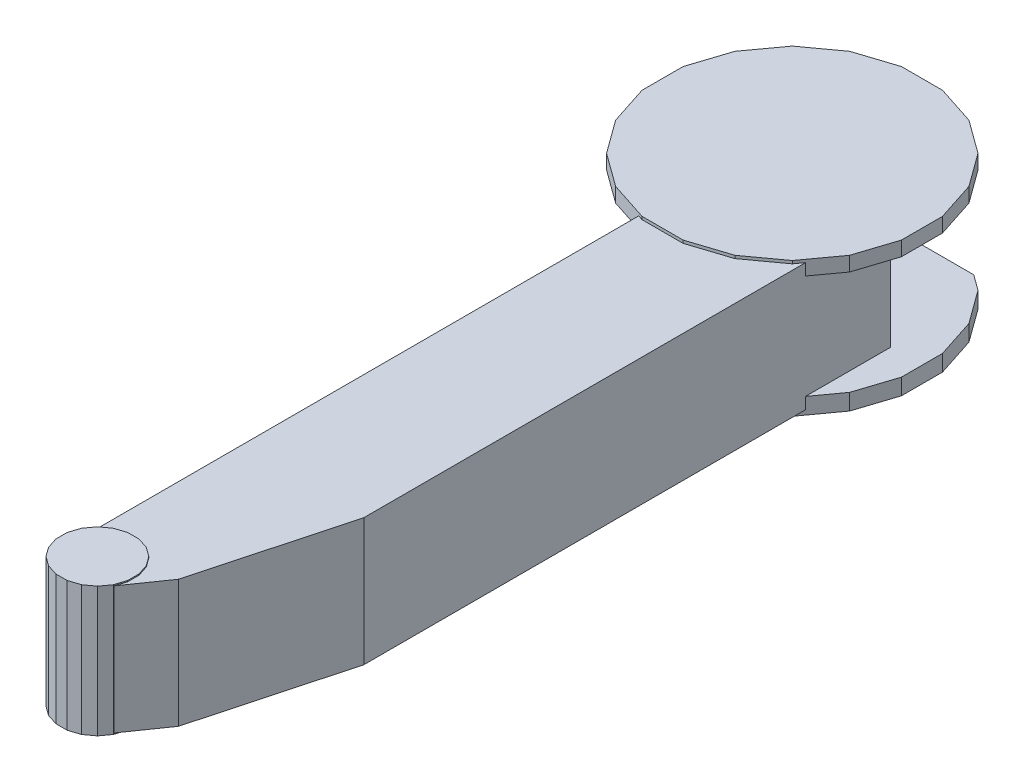
SolidWorks part; units mm, degrees
ref_plane "Front Plane" through (0, 0, 0) normal (0, 0, 1) x (1, 0, 0)
ref_plane "Top Plane" through (0, 0, 0) normal (0, 1, 0) x (1, 0, 0)
ref_plane "Right Plane" through (0, 0, 0) normal (1, 0, 0) x (0, 0, -1)
ref_plane "Plane1" through (0, -45, 0) normal (0, 1, 0) x (1, 0, 0)
sketch "Sketch1" plane through (0, -45, 0) normal (0, 1, 0) x (1, 0, 0)
  line L0 (101.0367, 51.4807) -> (85, 73.5533)
  line L1 (85, 73.5533) -> (85, 90)
  line L2 (85, 90) -> (66.6714, 90)
  line L3 (66.6714, 90) -> (51.4807, 101.0367)
  line L4 (51.4807, 101.0367) -> (17.7391, 112)
  line L5 (17.7391, 112) -> (-17.7391, 112)
  line L6 (-17.7391, 112) -> (-51.4807, 101.0367)
  line L7 (-51.4807, 101.0367) -> (-80.1831, 80.1831)
  line L8 (-80.1831, 80.1831) -> (-101.0367, 51.4807)
  line L9 (-101.0367, 51.4807) -> (-112, 17.7391)
  line L10 (-112, 17.7391) -> (-112, -17.7391)
  line L11 (-112, -17.7391) -> (-101.0367, -51.4807)
  line L12 (-101.0367, -51.4807) -> (-80.1831, -80.1831)
  line L13 (-80.1831, -80.1831) -> (-51.4807, -101.0367)
  line L14 (-51.4807, -101.0367) -> (-22, -110.6155)
  line L15 (-22, -110.6155) -> (-22, -577.6658)
  line L16 (-22, -577.6658) -> (-22.1935, -577.8065)
  line L17 (-22.1935, -577.8065) -> (-27.9655, -585.7509)
  line L18 (-27.9655, -585.7509) -> (-31, -595.0901)
  line L19 (-31, -595.0901) -> (-31, -604.9099)
  line L20 (-31, -604.9099) -> (-27.9655, -614.2491)
  line L21 (-27.9655, -614.2491) -> (-22.1935, -622.1935)
  line L22 (-22.1935, -622.1935) -> (-14.2491, -627.9655)
  line L23 (-14.2491, -627.9655) -> (-4.9099, -631)
  line L24 (-4.9099, -631) -> (4.9099, -631)
  line L25 (4.9099, -631) -> (14.2491, -627.9655)
  line L26 (14.2491, -627.9655) -> (22.1935, -622.1935)
  line L27 (22.1935, -622.1935) -> (27.9655, -614.2491)
  line L28 (27.9655, -614.2491) -> (28.0643, -613.945)
  line L29 (28.0643, -613.945) -> (51, -581)
  line L30 (51, -581) -> (85, -455)
  line L31 (85, -455) -> (85, -73.5533)
  line L32 (85, -73.5533) -> (101.0367, -51.4807)
  line L33 (101.0367, -51.4807) -> (112, -17.7391)
  line L34 (112, -17.7391) -> (112, 17.7391)
  line L35 (112, 17.7391) -> (101.0367, 51.4807)
extrude "Boss-Extrude1" add sketch "Sketch1" against normal blind 10
sketch "Sketch2" plane through (0, -45, 0) normal (0, 1, 0) x (-1, 0, 0)
  line L0 (-85, -90) -> (-85, 455)
  line L1 (-85, 455) -> (-51, 581)
  line L2 (-51, 581) -> (-28.0643, 613.945)
  line L3 (-28.0643, 613.945) -> (-27.9655, 614.2491)
  line L4 (-27.9655, 614.2491) -> (-22.1935, 622.1935)
  line L5 (-22.1935, 622.1935) -> (-14.2491, 627.9655)
  line L6 (-14.2491, 627.9655) -> (-4.9099, 631)
  line L7 (-4.9099, 631) -> (4.9099, 631)
  line L8 (4.9099, 631) -> (14.2491, 627.9655)
  line L9 (14.2491, 627.9655) -> (22.1935, 622.1935)
  line L10 (22.1935, 622.1935) -> (27.9655, 614.2491)
  line L11 (27.9655, 614.2491) -> (31, 604.9099)
  line L12 (31, 604.9099) -> (31, 595.0901)
  line L13 (31, 595.0901) -> (27.9655, 585.7509)
  line L14 (27.9655, 585.7509) -> (22.1935, 577.8065)
  line L15 (22.1935, 577.8065) -> (22, 577.6658)
  line L16 (22, 577.6658) -> (22, 110.6155)
  line L17 (22, 110.6155) -> (51.4807, 101.0367)
  line L18 (51.4807, 101.0367) -> (80.1831, 80.1831)
  line L19 (80.1831, 80.1831) -> (101.0367, 51.4807)
  line L20 (101.0367, 51.4807) -> (112, 17.7391)
  line L21 (112, 17.7391) -> (112, -17.7391)
  line L22 (112, -17.7391) -> (101.0367, -51.4807)
  line L23 (101.0367, -51.4807) -> (80.1831, -80.1831)
  line L24 (80.1831, -80.1831) -> (51.4807, -101.0367)
  line L25 (51.4807, -101.0367) -> (17.7391, -112)
  line L26 (17.7391, -112) -> (-17.7391, -112)
  line L27 (-17.7391, -112) -> (-51.4807, -101.0367)
  line L28 (-51.4807, -101.0367) -> (-66.6714, -90)
  line L29 (-66.6714, -90) -> (-85, -90)
extrude "Boss-Extrude2" add sketch "Sketch2" along normal blind 90
sketch "Sketch3" plane through (0, 45, 0) normal (0, 1, 0) x (-1, 0, 0)
  line L0 (-85, -73.5533) -> (-101.0367, -51.4807)
  line L1 (-101.0367, -51.4807) -> (-112, -17.7391)
  line L2 (-112, -17.7391) -> (-112, 17.7391)
  line L3 (-112, 17.7391) -> (-101.0367, 51.4807)
  line L4 (-101.0367, 51.4807) -> (-85, 73.5533)
  line L5 (-85, 73.5533) -> (-85, 455)
  line L6 (-85, 455) -> (-51, 581)
  line L7 (-51, 581) -> (-28.0643, 613.945)
  line L8 (-28.0643, 613.945) -> (-27.9655, 614.2491)
  line L9 (-27.9655, 614.2491) -> (-22.1935, 622.1935)
  line L10 (-22.1935, 622.1935) -> (-14.2491, 627.9655)
  line L11 (-14.2491, 627.9655) -> (-4.9099, 631)
  line L12 (-4.9099, 631) -> (4.9099, 631)
  line L13 (4.9099, 631) -> (14.2491, 627.9655)
  line L14 (14.2491, 627.9655) -> (22.1935, 622.1935)
  line L15 (22.1935, 622.1935) -> (27.9655, 614.2491)
  line L16 (27.9655, 614.2491) -> (31, 604.9099)
  line L17 (31, 604.9099) -> (31, 595.0901)
  line L18 (31, 595.0901) -> (27.9655, 585.7509)
  line L19 (27.9655, 585.7509) -> (22.1935, 577.8065)
  line L20 (22.1935, 577.8065) -> (22, 577.6658)
  line L21 (22, 577.6658) -> (22, 110.6155)
  line L22 (22, 110.6155) -> (51.4807, 101.0367)
  line L23 (51.4807, 101.0367) -> (80.1831, 80.1831)
  line L24 (80.1831, 80.1831) -> (101.0367, 51.4807)
  line L25 (101.0367, 51.4807) -> (112, 17.7391)
  line L26 (112, 17.7391) -> (112, -17.7391)
  line L27 (112, -17.7391) -> (101.0367, -51.4807)
  line L28 (101.0367, -51.4807) -> (80.1831, -80.1831)
  line L29 (80.1831, -80.1831) -> (51.4807, -101.0367)
  line L30 (51.4807, -101.0367) -> (17.7391, -112)
  line L31 (17.7391, -112) -> (-17.7391, -112)
  line L32 (-17.7391, -112) -> (-51.4807, -101.0367)
  line L33 (-51.4807, -101.0367) -> (-66.6714, -90)
  line L34 (-66.6714, -90) -> (-85, -90)
  line L35 (-85, -90) -> (-85, -73.5533)
extrude "Boss-Extrude3" add sketch "Sketch3" along normal blind 10
sketch "Sketch4" plane through (0, -55, 0) normal (0, -1, 0) x (1, 0, 0)
  line L0 (-30.0233, 89.4329) -> (-22, 89.4329)
  line L1 (-22, 89.4329) -> (-22, 110.6155)
  line L2 (-22, 110.6155) -> (-51.4807, 101.0367)
  line L3 (-51.4807, 101.0367) -> (-80.1831, 80.1831)
  line L4 (-80.1831, 80.1831) -> (-101.0367, 51.4807)
  line L5 (-101.0367, 51.4807) -> (-112, 17.7391)
  line L6 (-112, 17.7391) -> (-112, -17.7391)
  line L7 (-112, -17.7391) -> (-101.0367, -51.4807)
  line L8 (-101.0367, -51.4807) -> (-80.1831, -80.1831)
  line L9 (-80.1831, -80.1831) -> (-51.4807, -101.0367)
  line L10 (-51.4807, -101.0367) -> (-17.7391, -112)
  line L11 (-17.7391, -112) -> (17.7391, -112)
  line L12 (17.7391, -112) -> (51.4807, -101.0367)
  line L13 (51.4807, -101.0367) -> (66.6714, -90)
  line L14 (66.6714, -90) -> (-22, -90)
  line L15 (-22, -90) -> (-22, -87.4834)
  line L16 (-22, -87.4834) -> (-41.3685, -81.1902)
  line L17 (-41.3685, -81.1902) -> (-64.4329, -64.4329)
  line L18 (-64.4329, -64.4329) -> (-81.1902, -41.3685)
  line L19 (-81.1902, -41.3685) -> (-90, -14.2546)
  line L20 (-90, -14.2546) -> (-90, 14.2546)
  line L21 (-90, 14.2546) -> (-81.1902, 41.3685)
  line L22 (-81.1902, 41.3685) -> (-64.4329, 64.4329)
  line L23 (-64.4329, 64.4329) -> (-30.0233, 89.4329)
extrude "Cut-Extrude1" cut sketch "Sketch4" against normal blind 10
sketch "Sketch5" plane through (0, -45, 0) normal (0, -1, 0) x (1, 0, 0)
  line L0 (66.6714, -90) -> (-22, -90)
  line L1 (-22, -90) -> (-22, 110.6155)
  line L2 (-22, 110.6155) -> (-51.4807, 101.0367)
  line L3 (-51.4807, 101.0367) -> (-80.1831, 80.1831)
  line L4 (-80.1831, 80.1831) -> (-101.0367, 51.4807)
  line L5 (-101.0367, 51.4807) -> (-112, 17.7391)
  line L6 (-112, 17.7391) -> (-112, -17.7391)
  line L7 (-112, -17.7391) -> (-101.0367, -51.4807)
  line L8 (-101.0367, -51.4807) -> (-80.1831, -80.1831)
  line L9 (-80.1831, -80.1831) -> (-51.4807, -101.0367)
  line L10 (-51.4807, -101.0367) -> (-17.7391, -112)
  line L11 (-17.7391, -112) -> (17.7391, -112)
  line L12 (17.7391, -112) -> (51.4807, -101.0367)
  line L13 (51.4807, -101.0367) -> (66.6714, -90)
extrude "Cut-Extrude2" cut sketch "Sketch5" against normal blind 90
sketch "Sketch6" plane through (0, -55, 0) normal (0, -1, 0) x (1, 0, 0)
  line L0 (85, -90) -> (85, -73.5533)
  line L1 (85, -73.5533) -> (73.0508, -90)
  line L2 (73.0508, -90) -> (85, -90)
extrude "Cut-Extrude3" cut sketch "Sketch6" against normal blind 10
sketch "Sketch7" plane through (0, -55, 0) normal (0, -1, 0) x (1, 0, 0)
  line L0 (-14.2546, -90) -> (-22, -87.4834)
  line L1 (-22, -87.4834) -> (-22, -90)
  line L2 (-22, -90) -> (-14.2546, -90)
extrude "Cut-Extrude4" cut sketch "Sketch7" against normal blind 10
sketch "Sketch8" plane through (0, 55, 0) normal (0, 1, 0) x (-1, 0, 0)
  line L0 (-80.1831, -80.1831) -> (-85, -73.5533)
  line L1 (-85, -73.5533) -> (-85, -90)
  line L2 (-85, -90) -> (-66.6714, -90)
  line L3 (-66.6714, -90) -> (-80.1831, -80.1831)
extrude "Cut-Extrude5" cut sketch "Sketch8" against normal blind 10
sketch "Sketch9" plane through (0, 0, -90) normal (0, 0, -1) x (-1, 0, 0)
  line L0 (-80.1831, -45) -> (22, -45)
  line L1 (22, -45) -> (22, 45)
  line L2 (22, 45) -> (-80.1831, 45)
  line L3 (-80.1831, 45) -> (-85, 45)
  line L4 (-85, 45) -> (-85, -45)
  line L5 (-85, -45) -> (-80.1831, -45)
extrude "Cut-Extrude6" cut sketch "Sketch9" against normal blind 9.8169
sketch "Sketch10" plane through (0, 0, -80.1831) normal (0, 0, -1) x (-1, 0, 0)
  line L0 (-85, -45) -> (22, -45)
  line L1 (22, -45) -> (22, 45)
  line L2 (22, 45) -> (-85, 45)
  line L3 (-85, 45) -> (-85, -45)
extrude "Cut-Extrude7" cut sketch "Sketch10" against normal blind 80.1831
ref_plane "Plane2" through (0, 0, 89.4329) normal (0, 0, -1) x (-1, 0, 0)
sketch "Sketch11" plane through (0, 0, 89.4329) normal (0, 0, -1) x (-1, 0, 0)
  line L0 (22, -55) -> (22, -4)
  line L1 (22, -4) -> (16, -4)
  line L2 (16, -4) -> (16, -55)
  line L3 (16, -55) -> (22, -55)
extrude "Cut-Extrude8" cut sketch "Sketch11" against normal blind 134.5671
sketch "Sketch12" plane through (0, -55, 0) normal (0, -1, 0) x (1, 0, 0)
  line L0 (-16, 89.4329) -> (-16, 112)
  line L1 (-16, 112) -> (17.7391, 112)
  line L2 (17.7391, 112) -> (51.4807, 101.0367)
  line L3 (51.4807, 101.0367) -> (80.1831, 80.1831)
  line L4 (80.1831, 80.1831) -> (101.0367, 51.4807)
  line L5 (101.0367, 51.4807) -> (112, 17.7391)
  line L6 (112, 17.7391) -> (112, -17.7391)
  line L7 (112, -17.7391) -> (101.0367, -51.4807)
  line L8 (101.0367, -51.4807) -> (73.0508, -90)
  line L9 (73.0508, -90) -> (-14.2546, -90)
  line L10 (-14.2546, -90) -> (-41.3685, -81.1902)
  line L11 (-41.3685, -81.1902) -> (-64.4329, -64.4329)
  line L12 (-64.4329, -64.4329) -> (-81.1902, -41.3685)
  line L13 (-81.1902, -41.3685) -> (-90, -14.2546)
  line L14 (-90, -14.2546) -> (-90, 14.2546)
  line L15 (-90, 14.2546) -> (-81.1902, 41.3685)
  line L16 (-81.1902, 41.3685) -> (-64.4329, 64.4329)
  line L17 (-64.4329, 64.4329) -> (-30.0233, 89.4329)
  line L18 (-30.0233, 89.4329) -> (-16, 89.4329)
extrude "Boss-Extrude4" add sketch "Sketch12" along normal blind 4
sketch "Sketch13" plane through (0, -55, 0) normal (0, -1, 0) x (1, 0, 0)
  line L0 (22.1935, 577.8065) -> (14.2491, 572.0345)
  line L1 (14.2491, 572.0345) -> (4.9099, 569)
  line L2 (4.9099, 569) -> (-4.9099, 569)
  line L3 (-4.9099, 569) -> (-14.2491, 572.0345)
  line L4 (-14.2491, 572.0345) -> (-22.1935, 577.8065)
  line L5 (-22.1935, 577.8065) -> (-27.9655, 585.7509)
  line L6 (-27.9655, 585.7509) -> (-31, 595.0901)
  line L7 (-31, 595.0901) -> (-31, 604.9099)
  line L8 (-31, 604.9099) -> (-27.9655, 614.2491)
  line L9 (-27.9655, 614.2491) -> (-22.1935, 622.1935)
  line L10 (-22.1935, 622.1935) -> (-14.2491, 627.9655)
  line L11 (-14.2491, 627.9655) -> (-4.9099, 631)
  line L12 (-4.9099, 631) -> (4.9099, 631)
  line L13 (4.9099, 631) -> (14.2491, 627.9655)
  line L14 (14.2491, 627.9655) -> (22.1935, 622.1935)
  line L15 (22.1935, 622.1935) -> (27.9655, 614.2491)
  line L16 (27.9655, 614.2491) -> (31, 604.9099)
  line L17 (31, 604.9099) -> (31, 595.0901)
  line L18 (31, 595.0901) -> (27.9655, 585.7509)
  line L19 (27.9655, 585.7509) -> (22.1935, 577.8065)
extrude "Boss-Extrude5" add sketch "Sketch13" along normal blind 1
sketch "Sketch14" plane through (0, 55, 0) normal (0, 1, 0) x (-1, 0, 0)
  line L0 (-14.2491, 572.0345) -> (-22.1935, 577.8065)
  line L1 (-22.1935, 577.8065) -> (-27.9655, 585.7509)
  line L2 (-27.9655, 585.7509) -> (-31, 595.0901)
  line L3 (-31, 595.0901) -> (-31, 604.9099)
  line L4 (-31, 604.9099) -> (-27.9655, 614.2491)
  line L5 (-27.9655, 614.2491) -> (-22.1935, 622.1935)
  line L6 (-22.1935, 622.1935) -> (-14.2491, 627.9655)
  line L7 (-14.2491, 627.9655) -> (-4.9099, 631)
  line L8 (-4.9099, 631) -> (4.9099, 631)
  line L9 (4.9099, 631) -> (14.2491, 627.9655)
  line L10 (14.2491, 627.9655) -> (22.1935, 622.1935)
  line L11 (22.1935, 622.1935) -> (27.9655, 614.2491)
  line L12 (27.9655, 614.2491) -> (31, 604.9099)
  line L13 (31, 604.9099) -> (31, 595.0901)
  line L14 (31, 595.0901) -> (27.9655, 585.7509)
  line L15 (27.9655, 585.7509) -> (22.1935, 577.8065)
  line L16 (22.1935, 577.8065) -> (14.2491, 572.0345)
  line L17 (14.2491, 572.0345) -> (4.9099, 569)
  line L18 (4.9099, 569) -> (-4.9099, 569)
  line L19 (-4.9099, 569) -> (-14.2491, 572.0345)
extrude "Boss-Extrude6" add sketch "Sketch14" along normal blind 1
sketch "Sketch15" plane through (0, 55, 0) normal (0, 1, 0) x (-1, 0, 0)
  line L0 (-80.1831, -80.1831) -> (-101.0367, -51.4807)
  line L1 (-101.0367, -51.4807) -> (-112, -17.7391)
  line L2 (-112, -17.7391) -> (-112, 17.7391)
  line L3 (-112, 17.7391) -> (-101.0367, 51.4807)
  line L4 (-101.0367, 51.4807) -> (-80.1831, 80.1831)
  line L5 (-80.1831, 80.1831) -> (-51.4807, 101.0367)
  line L6 (-51.4807, 101.0367) -> (-17.7391, 112)
  line L7 (-17.7391, 112) -> (17.7391, 112)
  line L8 (17.7391, 112) -> (51.4807, 101.0367)
  line L9 (51.4807, 101.0367) -> (80.1831, 80.1831)
  line L10 (80.1831, 80.1831) -> (101.0367, 51.4807)
  line L11 (101.0367, 51.4807) -> (112, 17.7391)
  line L12 (112, 17.7391) -> (112, -17.7391)
  line L13 (112, -17.7391) -> (101.0367, -51.4807)
  line L14 (101.0367, -51.4807) -> (80.1831, -80.1831)
  line L15 (80.1831, -80.1831) -> (51.4807, -101.0367)
  line L16 (51.4807, -101.0367) -> (17.7391, -112)
  line L17 (17.7391, -112) -> (-17.7391, -112)
  line L18 (-17.7391, -112) -> (-51.4807, -101.0367)
  line L19 (-51.4807, -101.0367) -> (-80.1831, -80.1831)
extrude "Boss-Extrude7" add sketch "Sketch15" along normal blind 2.5
draft "Draft1" type of draft neutral plane draft angle 18 faces to draft 1 face at (-22.6744, -36, 89.4329) neutral plane through (-16, -4, 224) neutral plane normal (-1, 0, 0) parameters "D1"=18
chamfer "Chamfer1" distance 6.3794 angle 36 1 edges at (73.0508, -52, -90) first distance on face at (29.3981, -52, -90)
ref_axis "Axis1" through (0, 63.325, 0) along (0, -1, 0)
sketch "Sketch16" plane through (0, -56, 0) normal (0, -1, 0) x (1, 0, 0)
  line L0 (4.9099, 631) -> (-4.9099, 631) construction
  line L1 (-27.9655, 585.7509) -> (-22.1935, 577.8065) construction
  line L2 (22.1935, 577.8065) -> (27.9655, 585.7509) construction
  circle A0 centre (0, 600) radius 31
ref_axis "Axis2" through (0, -56, 600) along (0, 1, 0)
